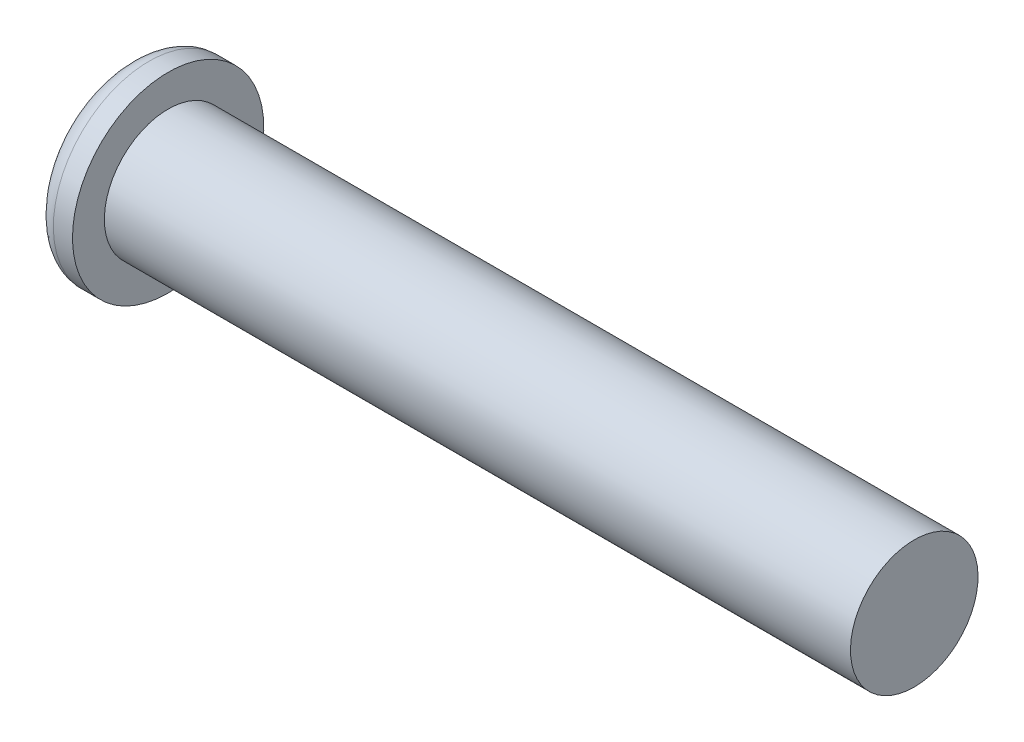
SolidWorks part; units mm, degrees
ref_plane "Front Plane" through (0, 0, 0) normal (0, 0, 1) x (1, 0, 0)
ref_plane "Top Plane" through (0, 0, 0) normal (0, 1, 0) x (1, 0, 0)
ref_plane "Right Plane" through (0, 0, 0) normal (1, 0, 0) x (0, 0, -1)
sketch "Sketch1" plane through (0, 0, 0) normal (0, 0, 1) x (1, 0, 0)
  line L0 (0, 0) -> (58.5, 0) construction
  line L1 (58.5, 0) -> (58.5, 5)
  line L2 (58.5, 5) -> (0, 5)
  line L3 (0, 5) -> (0, 7.5)
  line L4 (0, 7.5) -> (-1.5, 7.5)
  line L5 (-1.5, 7.5) -> (-1.5, 0)
  line L6 (-1.5, 0) -> (58.5, 0)
  dimension "D1" = 5
  dimension "D2" = 58.5
  dimension "D3" = 7.5
  dimension "D4" = 1.5
revolve "Revolve1" add sketch "Sketch1" angle 360 about L0
dome "Dome1" faces to dome 1 distance 3 reverse direction no elliptical dome yes face at (-1.5, -7.5, 0) parameters "D1"=3
